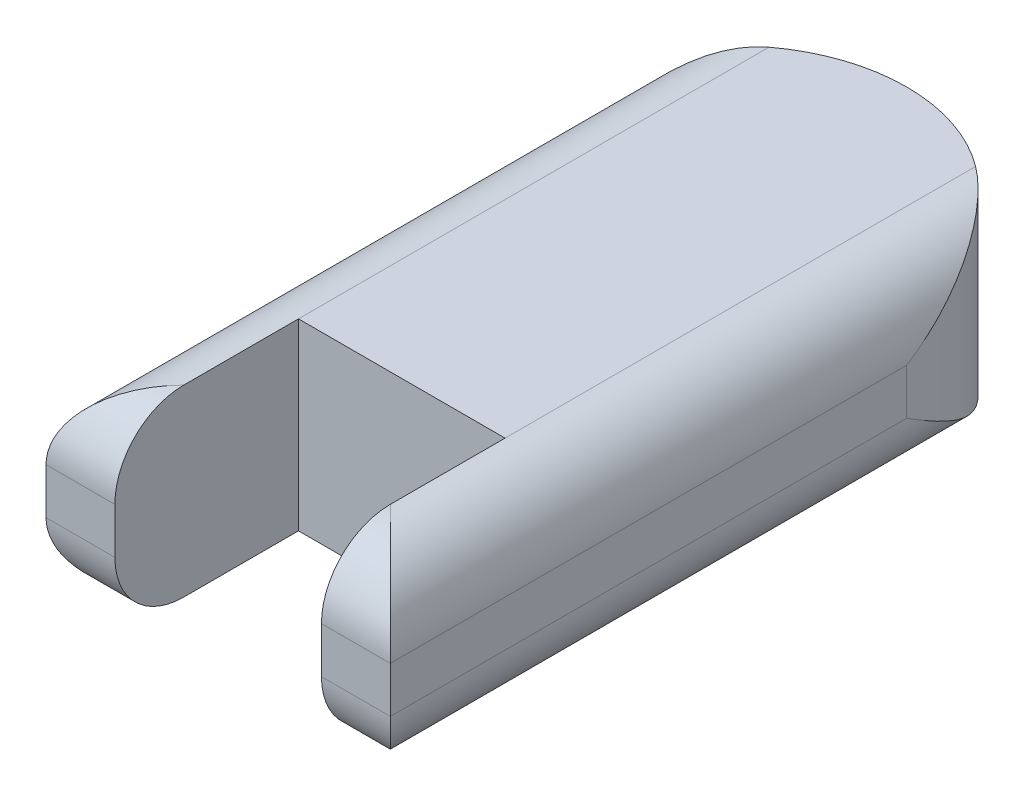
SolidWorks part; units mm, degrees
ref_plane "Alzado" through (0, 0, 0) normal (0, 0, 1) x (1, 0, 0)
ref_plane "Planta" through (0, 0, 0) normal (0, 1, 0) x (1, 0, 0)
ref_plane "Vista lateral" through (0, 0, 0) normal (1, 0, 0) x (0, 0, -1)
sketch "Sketch1" plane through (0, 0, 0) normal (0, 0, 1) x (1, 0, 0)
  line L1 (-45, -40) -> (45, -40)
  line L2 (-75, -10) -> (-75, 10)
  line L3 (-45, 40) -> (45, 40)
  line L4 (75, -10) -> (75, 10)
  line L5 (-75, -40) -> (75, 40) construction
  line L6 (-75, 40) -> (75, -40) construction
  arc A0 (-75, 10) -> (-45, 40) centre (-45, 10) cw
  arc A1 (45, -40) -> (75, -10) centre (45, -10) ccw
  arc A2 (-45, -40) -> (-75, -10) centre (-45, -10) cw
  arc A3 (45, 40) -> (75, 10) centre (45, 10) cw
  point P0 (0, 0)
  dimension "D3" = 30
  dimension "D4" = 30
  dimension "D1" = 150
  dimension "D2" = 80
extrude "Boss-Extrude1" add sketch "Sketch1" along normal blind 150 and the other way blind 150
sketch "Sketch2" plane through (75, 0, 0) normal (1, 0, 0) x (0, 0, -1)
  line L1 (150, 40) -> (-120, 40)
  line L2 (150, 40) -> (150, -40)
  line L3 (150, -40) -> (-120, -40)
  line L4 (-150, 10) -> (-150, -10)
  arc A0 (-120, -40) -> (-150, -10) centre (-120, -10) cw
  arc A1 (-120, 40) -> (-150, 10) centre (-120, 10) ccw
  point P8 (-150, -40)
  dimension "D1" = 30
extrude "Cut-Extrude1" cut sketch "Sketch2" against normal blind 150 flip side to cut
sketch "Sketch3" plane through (0, -40, 0) normal (0, -1, 0) x (1, 0, 0)
  line L1 (-45, 150) -> (45, 150)
  line L2 (-45, 150) -> (-45, 70)
  line L3 (-45, 70) -> (45, 70)
  line L4 (45, 150) -> (45, 70)
  line L5 (-75, 150) -> (75, 150) construction
  line L6 (-45, 120) -> (-45, -150) construction
  line L7 (45, 120) -> (45, -150) construction
  dimension "D1" = 80
extrude "Cut-Extrude2" cut sketch "Sketch3" against normal up to next
sketch "Sketch4" plane through (-45, 0, 0) normal (1, 0, 0) x (0, 0, -1)
  line L0 (-70, 0) -> (-150, 0) construction
  line L1 (-70, 40) -> (-70, -40) construction
  line L3 (-110, -10) -> (-110, -39.4509) construction
  point P3 (-70, 0)
  point P4 (-110, 0)
  dimension "D1" = 40
ref_axis "Axis2" through (-45, 0, 110) along (1, 0, 0)
sketch "Sketch6" plane through (0, 40, 0) normal (0, 1, 0) x (1, 0, 0)
  line L0 (-75, 75) -> (-75, 0)
  line L5 (-75, 150) -> (-75, -150) construction
  line L7 (75, 150) -> (75, -150) construction
  line L8 (75, 0) -> (75, 75)
  line L9 (45, 150) -> (-45, 150) construction
  line L12 (-75, 0) -> (-75, -150)
  line L13 (-75, -150) -> (75, -150)
  line L14 (75, 0) -> (75, -150)
  arc A0 (-75, 75) -> (75, 75) centre (0, 75) cw
  dimension "D1" = 75
extrude "Cut-Extrude3" cut sketch "Sketch6" against normal through all flip side to cut
sketch "Sketch7" plane through (0, 40, 0) normal (0, 1, 0) x (1, 0, 0)
  point P0 (0, 75)
  dimension "D1" = 75
ref_axis "Axis1" through (0, 40, -75) along (0, 1, 0)
